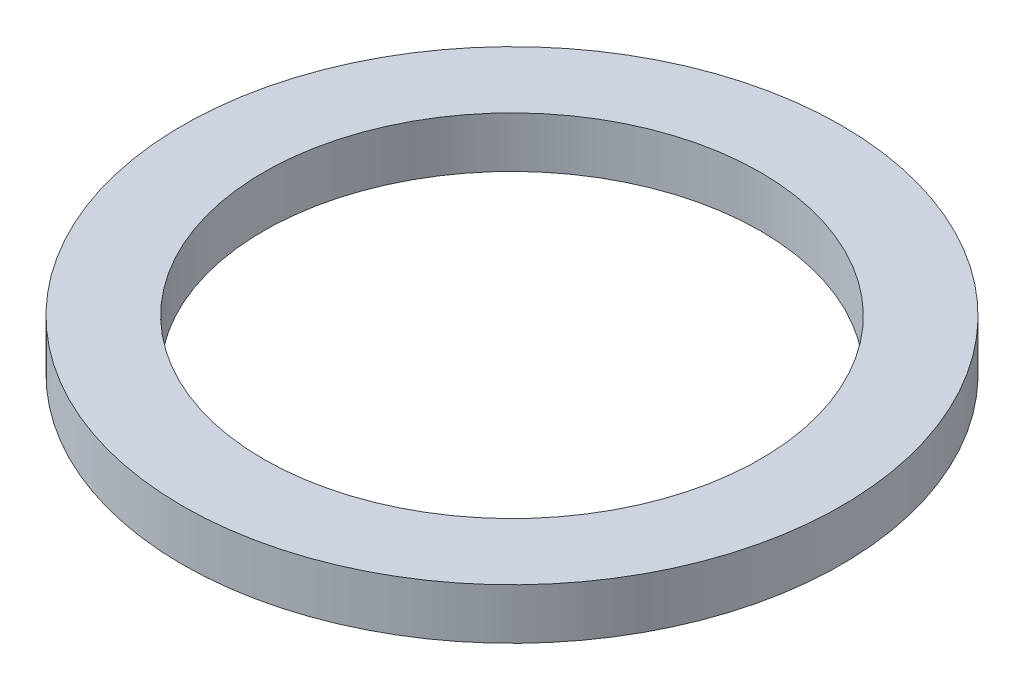
SolidWorks part; units mm, degrees
ref_plane "Front Plane" through (0, 0, 0) normal (0, 0, 1) x (1, 0, 0)
ref_plane "Top Plane" through (0, 0, 0) normal (0, 1, 0) x (1, 0, 0)
ref_plane "Right Plane" through (0, 0, 0) normal (1, 0, 0) x (0, 0, -1)
sketch "Sketch1" plane through (0, 0, 0) normal (0, 1, 0) x (1, 0, 0)
  circle A0 centre (0, 0) radius 32.5
  circle A1 centre (0, 0) radius 24.5
  dimension "D1" = 65
  dimension "D2" = 8
extrude "Boss-Extrude1" add sketch "Sketch1" along normal blind 5
sketch "Sketch2" plane through (0, 5, 0) normal (0, 1, 0) x (1, 0, 0)
  circle A0 centre (0, 22.5) radius 2.25
  circle A1 centre (-12.5, -20) radius 2.25
  circle A2 centre (12.5, -20) radius 2.25
  circle A3 centre (-14.7776, 12.7229) radius 1.5
  circle A4 centre (0, 0) radius 19.5 construction
  circle A6 centre (0, 0) radius 24.5 construction
  circle A7 centre (-16.074, -11.0397) radius 1.5
  point P13 (-16.074, -11.0397)
  point P16 (-14.7776, 12.7229)
  dimension "D5" = 4.5
  dimension "D6" = 4.5
  dimension "D7" = 4.5
  dimension "D8" = 3
  dimension "D10" = 3
  dimension "D1" = 25
  dimension "D2" = 12.5
  dimension "D3" = 22.5
  dimension "D4" = 20
  dimension "D9" = 5
equation "\"D2@Sketch2\"=\"D1@Sketch2\"/2"
equation "\"D6@Sketch2\"=\"D5@Sketch2\""
equation "\"D7@Sketch2\"=\"D6@Sketch2\""
equation "\"D10@Sketch2\"=\"D8@Sketch2\""
